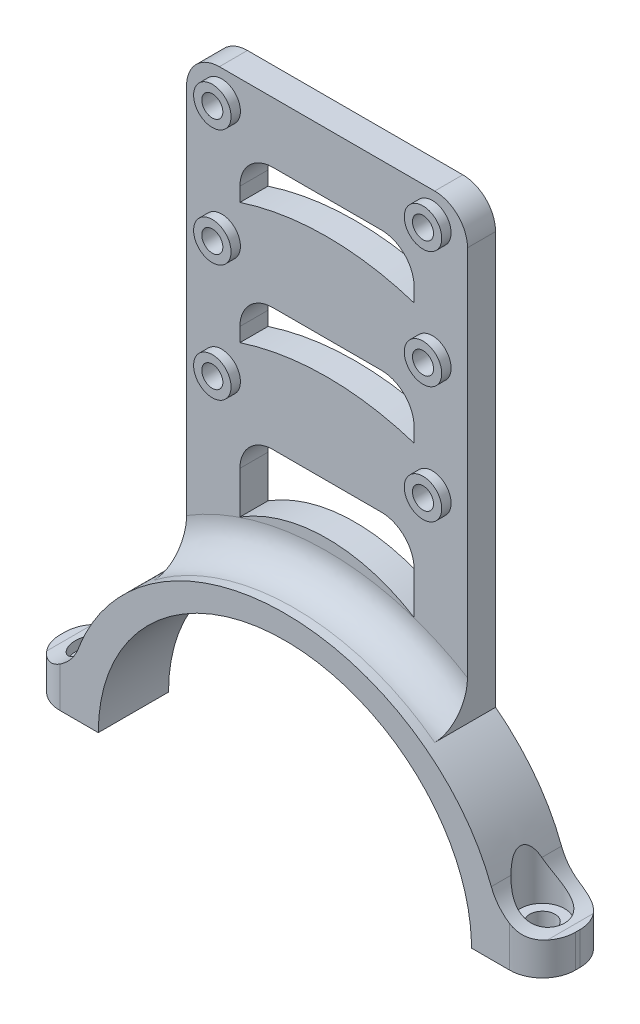
SolidWorks part; units mm, degrees
ref_plane "Front Plane" through (0, 0, 0) normal (0, 0, 1) x (1, 0, 0)
ref_plane "Top Plane" through (0, 0, 0) normal (0, 1, 0) x (1, 0, 0)
ref_plane "Right Plane" through (0, 0, 0) normal (1, 0, 0) x (0, 0, -1)
sketch "Sketch1" plane through (0, 0, 0) normal (0, 0, 1) x (1, 0, 0)
  line L0 (-39.855, 0) -> (-55.0244, 0)
  line L1 (39.855, 0) -> (55.0244, 0)
  line L2 (-55.0244, 0) -> (-55.0244, 7.0113)
  line L3 (55.0244, 0) -> (55.0244, 7.0113)
  line L4 (-55.0244, 7.0113) -> (-45.9009, 6.9897)
  line L5 (45.9009, 6.9897) -> (55.0244, 7.0113)
  ellipse E0 centre (0, 0) end of major axis (39.855, 0) minor radius 37 (-39.855, 0) -> (39.855, 0) cw
  ellipse E1 centre (0, 0) end of major axis (-46.5501, 0) minor radius 42 (-45.9009, 6.9897) -> (45.9009, 6.9897) cw
  dimension "D1" = 79.71
  dimension "D2" = 37
  dimension "D3" = 5
extrude "Boss-Extrude1" add sketch "Sketch1" along normal blind 15
fillet "Fillet1" radius 10 2 edges at (45.9009, 6.9897, 7.5) (-45.9009, 6.9897, 7.5)
sketch "Sketch3" plane through (0, 0, 0) normal (0, 1, 0) x (1, 0, 0)
  line L0 (0, 0) -> (0, -44.399) construction
  circle A0 centre (47.5, -7.5) radius 2.7
  circle A1 centre (-47.5, -7.5) radius 2.7
  point P4 (0, 0)
  point P5 (0, 0)
  dimension "D1" = 5.4
  dimension "D2" = 95
extrude "Cut-Extrude1" cut sketch "Sketch3" along normal blind 17 contours A1
extrude "Cut-Extrude2" cut sketch "Sketch3<4>" along normal blind 12 and the other way blind 1
sketch "Sketch3<4>" plane through (0, 0, 0) normal (0, 1, 0) x (1, 0, 0) same geometry as "Sketch3"
ref_plane "Plane1" through (0, 5, 0) normal (0, 1, 0) x (1, 0, 0)
sketch "Sketch5" plane through (0, 5, 0) normal (0, 1, 0) x (1, 0, 0)
  circle A0 centre (-47.5, -7.5) radius 4.75
  circle A1 centre (47.5, -7.5) radius 4.75
  dimension "D1" = 9.5
  dimension "D2" = 9.5
extrude "Cut-Extrude3" cut sketch "Sketch5" along normal blind 17
sketch "Sketch6" plane through (0, 0, 0) normal (0, 0, 1) x (1, 0, 0)
  line L0 (18.6004, 62.0168) -> (18.6004, 46.0168)
  line L1 (30, 127.1145) -> (-30, 127.1145)
  line L3 (-18.6004, 62.0168) -> (-18.6004, 46.0168)
  line L4 (30, 32.1145) -> (30, 127.1145)
  line L5 (-30, 32.1145) -> (-30, 127.1145)
  line L8 (18.6004, 88.2664) -> (18.6004, 78.2664)
  line L9 (-18.6004, 78.2664) -> (-18.6004, 88.2664)
  line L10 (-18.6004, 114.2107) -> (-18.6004, 104.2107)
  line L11 (18.6004, 114.2107) -> (18.6004, 104.2107)
  line L12 (18.6004, 114.2107) -> (-18.6004, 114.2107)
  line L13 (18.6004, 88.2664) -> (-18.6004, 88.2664)
  line L14 (18.6004, 62.0168) -> (-18.6004, 62.0168)
  circle A0 centre (22.5, 121.1145) radius 2.25
  circle A1 centre (-22.5, 121.1145) radius 2.25
  circle A2 centre (-22.5, 96.1145) radius 2.25
  circle A3 centre (-22.5, 71.1145) radius 2.25
  circle A4 centre (22.5, 96.1145) radius 2.25
  circle A5 centre (22.5, 71.1145) radius 2.25
  arc A10 (-18.6004, 78.2664) -> (18.6004, 78.2664) centre (0, 21.2223) cw
  arc A12 (30, 32.1145) -> (-30, 32.1145) centre (0, -13.9832) ccw
  arc A13 (18.6004, 104.2107) -> (-18.6004, 104.2107) centre (0, 47.1666) ccw
  arc A14 (18.6004, 46.0168) -> (-18.6004, 46.0168) centre (0, 16.3685) ccw
  ellipse E0 centre (0, 0) end of major axis (-46.5501, 0) minor radius 42 (44.0839, 13.4891) -> (-44.0839, 13.4891) ccw construction
  point P10 (0, 81.2223)
  dimension "D7" = 4.5
  dimension "D9" = 4.5
  dimension "D10" = 4.5
  dimension "D23" = 60
  dimension "D4" = 16
  dimension "D17" = 55
  dimension "D18" = 60
  dimension "D19" = 60
  dimension "D13" = 35
  dimension "D1" = 60
  dimension "D2" = 95
  dimension "D3" = 95
  dimension "D5" = 10
  dimension "D6" = 45
  dimension "D8" = 6
  dimension "D11" = 25
  dimension "D12" = 25
  dimension "D14" = 10
  dimension "D15" = 10
  dimension "D16" = 10
extrude "Boss-Extrude6" add sketch "Sketch6" along normal blind 6
fillet "Fillet7" radius 7 8 edges at (-18.6004, 62.0168, 3) (18.6004, 62.0168, 3) (18.6004, 88.2664, 3) (-18.6004, 88.2664, 3) (-18.6004, 114.2107, 3) (18.6004, 114.2107, 3) (30, 127.1145, 3) (-30, 127.1145, 3)
fillet "Fillet8" radius 7 2 edges at (-55.0244, 3.5056, 15) (-55.0244, 3.5056, 0)
fillet "Fillet9" radius 7 2 edges at (55.0244, 3.5056, 15) (55.0244, 3.5056, 0)
fillet "Fillet10" radius 7 1 edges at (0, 42, 6)
ref_plane "Plane6" through (0, 0, 6) normal (0, 0, 1) x (1, 0, 0)
sketch "Sketch8" plane through (0, 0, 6) normal (0, 0, 1) x (1, 0, 0)
  circle A0 centre (-22.5, 121.1145) radius 4
  circle A1 centre (22.5, 121.1145) radius 4
  circle A2 centre (-22.5, 96.1145) radius 4
  circle A3 centre (22.5, 96.1145) radius 4
  circle A4 centre (22.5, 71.1145) radius 4
  circle A5 centre (-22.5, 71.1145) radius 4
  circle A6 centre (-22.5, 121.1145) radius 2.25
  circle A7 centre (22.5, 121.1145) radius 2.25
  circle A8 centre (-22.5, 96.1145) radius 2.25
  circle A9 centre (22.5, 96.1145) radius 2.25
  circle A10 centre (22.5, 71.1145) radius 2.25
  circle A11 centre (-22.5, 71.1145) radius 2.25
  dimension "D1" = 8
  dimension "D2" = 8
  dimension "D3" = 8
  dimension "D4" = 8
  dimension "D5" = 8
  dimension "D6" = 8
extrude "Boss-Extrude7" add sketch "Sketch8" along normal blind 2
